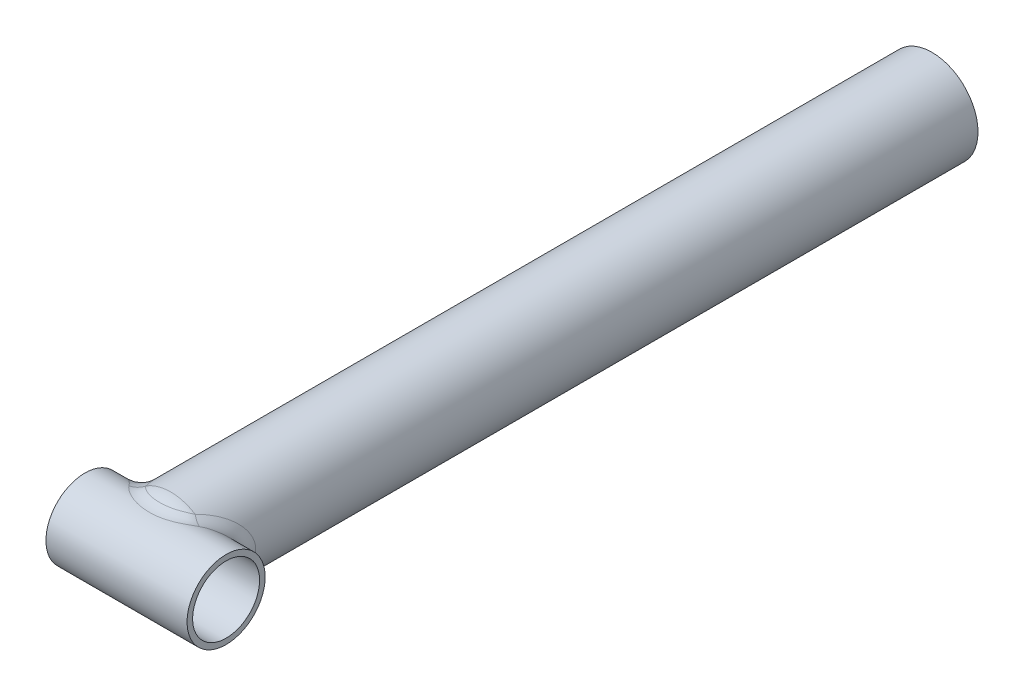
SolidWorks part; units mm, degrees
ref_plane "Front Plane" through (0, 0, 0) normal (0, 0, 1) x (1, 0, 0)
ref_plane "Top Plane" through (0, 0, 0) normal (0, 1, 0) x (1, 0, 0)
ref_plane "Right Plane" through (0, 0, 0) normal (1, 0, 0) x (0, 0, -1)
sketch "Sketch1" plane through (0, 0, 0) normal (0, 0, 1) x (1, 0, 0)
  circle A0 centre (0, 0) radius 23.55
  dimension "D1" = 47.1
extrude "Boss-Extrude1" add sketch "Sketch1" against normal blind 400
sketch "Sketch2" plane through (0, 0, 0) normal (1, 0, 0) x (0, 0, -1)
  circle A0 centre (0, 0) radius 20
  circle A1 centre (0, 0) radius 17.15
  dimension "D1" = 40
  dimension "D2" = 34.3
extrude "Boss-Extrude2" add sketch "Sketch2" along normal blind 72.3 from offset 33.9 offset against normal yes
fillet "Fillet1" radius 10 3 edges at (23.3835, -2.7958, -19.8036) (0, 23.55, 0) (0, 20, 0)
fillet "Fillet2" radius 10 1 edges at (0, -23.55, 0)
sketch "Sketch3" plane through (0, 0, 0) normal (1, 0, 0) x (0, 0, -1)
  circle A0 centre (0, 0) radius 17.15
  dimension "D1" = 34.3
extrude "Cut-Extrude1" cut sketch "Sketch3" against normal through all from offset 60
fillet "Fillet3" radius 10 4 edges at (23.3878, 2.7591, -19.8088) (-23.3878, -2.7591, -19.8088) (0, 19.8727, -2.2526) (0, -19.8727, -2.2526)
